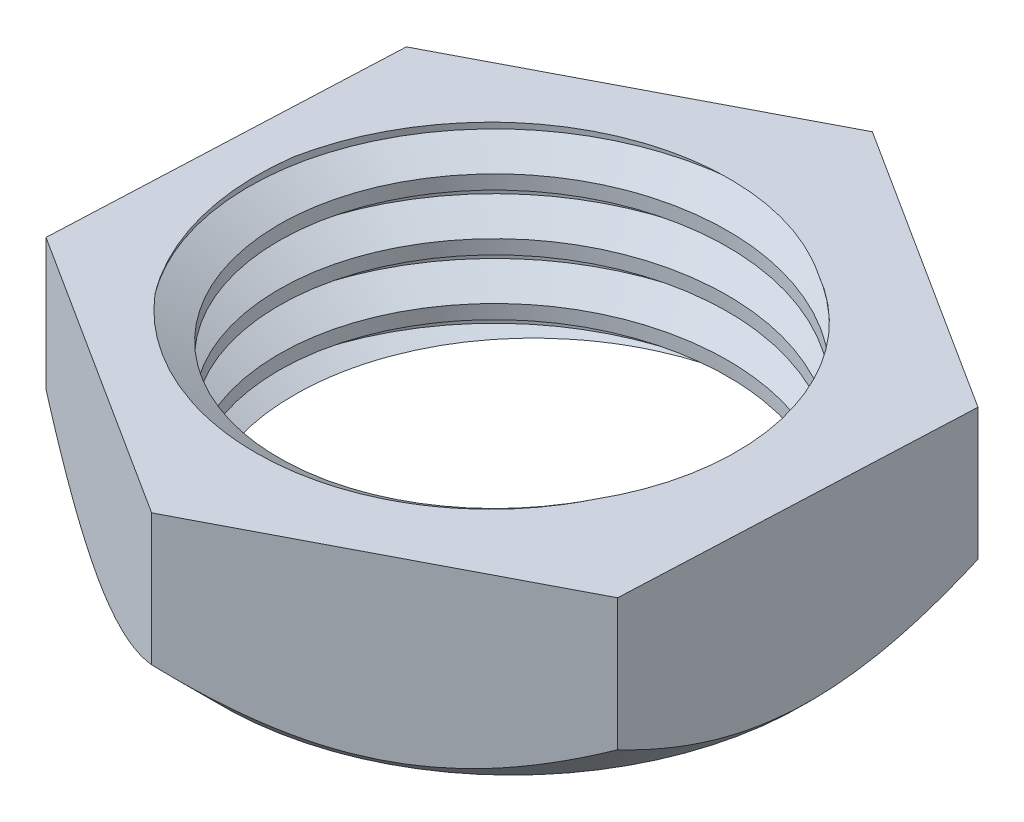
SolidWorks part; units mm, degrees
ref_plane "Front Plane" through (0, 0, 0) normal (0, 0, 1) x (1, 0, 0)
ref_plane "Top Plane" through (0, 0, 0) normal (0, 1, 0) x (1, 0, 0)
ref_plane "Right Plane" through (0, 0, 0) normal (1, 0, 0) x (0, 0, -1)
sketch "Sketch1" plane through (0, 0, 0) normal (0, 1, 0) x (1, 0, 0)
  line L1 (7.7896, -4.9655) -> (8.195, 4.2632)
  line L2 (8.195, 4.2632) -> (0.4054, 9.2287)
  line L3 (0.4054, 9.2287) -> (-7.7896, 4.9655)
  line L4 (-7.7896, 4.9655) -> (-8.195, -4.2632)
  line L5 (-8.195, -4.2632) -> (-0.4054, -9.2287)
  line L6 (-0.4054, -9.2287) -> (7.7896, -4.9655)
  circle A0 centre (0, 0) radius 8 construction
  circle A1 centre (0, 0) radius 6
  dimension "D2" = 12
  dimension "D1" = 16
extrude "Boss-Extrude1" add sketch "Sketch1" along normal blind 5
thread "Thread1" pitch 1.5 method cut trim with start face yes trim with end face yes profile "Thread Profile1" start angle 0, offset 5, length 14.76, pitch 1.5, diameter 12
ref_plane "Plane1" through (-6, 10, 0) normal (0, 0, 1) x (-1, 0, 0)
sketch "Thread Profile1" plane through (-6, 10, 0) normal (0, 0, 1) x (-1, 0, 0)
  line L0 (0, 0) -> (0, 1.5) construction
  line L1 (0, 0) -> (0.8119, 0.4687)
  line L2 (0.8119, 0.4687) -> (0.8119, 0.6562)
  line L3 (0.8119, 0.6562) -> (0, 1.125)
  line L4 (0.8119, 0.5625) -> (0, 0.5625) construction
  line L11 (0, 0) -> (0, 1.125)
  point P2 (0, 0)
  dimension "Pitch" = 1.5
  dimension "Profile_Angle" = 60
  dimension "Profile_Land" = 0.1875
  dimension "Profile_Height" = 0.8119
sketch "Sketch5" plane through (0, 0, 0) normal (0, -1, 0) x (-1, 0, 0)
  circle A0 centre (0, 0) radius 7.7563
extrude "Cut-Extrude1" cut sketch "Sketch5" against normal blind 10 draft 45 flip side to cut
